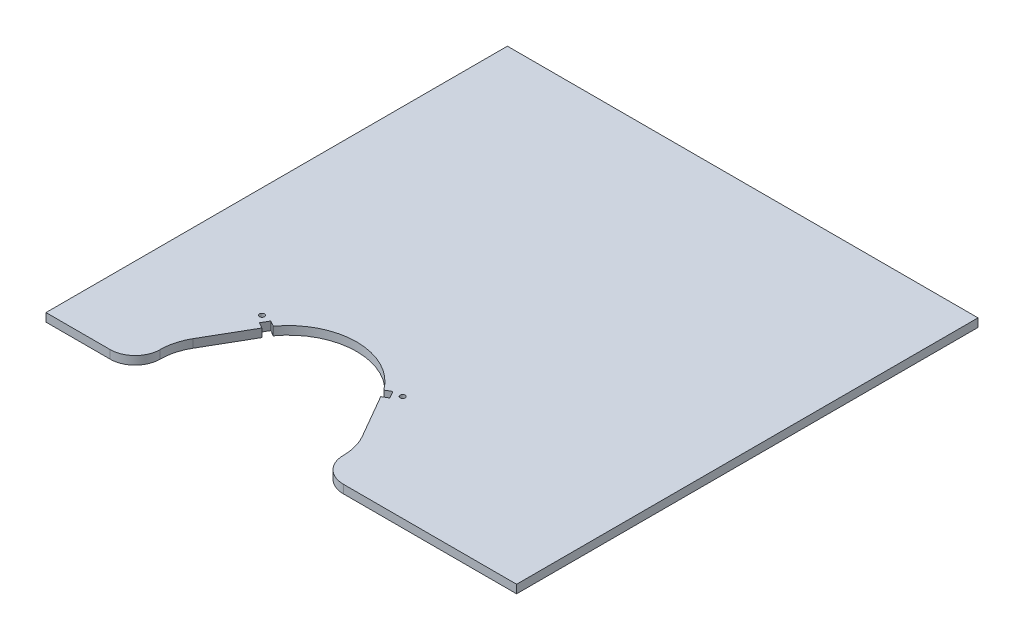
SolidWorks part; units mm, degrees
material "ABS PC"
ref_plane "Plan de face" through (0, 0, 0) normal (0, 0, 1) x (1, 0, 0)
ref_plane "Plan de dessus" through (0, 0, 0) normal (0, 1, 0) x (1, 0, 0)
ref_plane "Plan de droite" through (0, 0, 0) normal (1, 0, 0) x (0, 0, -1)
sketch "Esquisse1" plane through (0, 0, 0) normal (0, 1, 0) x (1, 0, 0)
  line L1 (-140.5, 31.9) -> (141.9979, 31.9)
  line L2 (-140.5, 31.9) -> (-140.5, -245.0829)
  line L3 (-140.5, -245.0829) -> (141.9979, -245.0829)
  line L4 (141.9979, 31.9) -> (141.9979, -245.0829)
  line L5 (38, -245.0829) -> (54.7016, -245.0829) construction
  line L6 (99.5, 31.9) -> (113.5, 31.9) construction
  arc A0 (-32, -23.5) -> (-95.029, -220.3153) centre (-32, -132) ccw construction
extrude "Boss.-Extru.1" add sketch "Esquisse1" along normal blind 5
sketch "Esquisse2" plane through (0, 0, 0) normal (0, 1, 0) x (1, 0, 0)
  line L3 (-65.1815, -184) -> (-68.6457, -182)
  line L4 (-68.6457, -182) -> (-71.1457, -186.3301)
  line L5 (-71.1457, -186.3301) -> (-67.6815, -188.3301)
  line L7 (-32, -132) -> (-32, -245.0829) construction
  line L8 (-65.1815, -184) -> (-67.6815, -188.3301) construction
  line L9 (-62.6323, -132) -> (62.6323, -132) construction
  line L10 (-32, -62.6323) -> (-32, 62.6323) construction
  line L11 (-67.6815, -188.3301) -> (-82.8539, -214.6094)
  line L13 (-65.1815, -184) -> (-61.7174, -186) construction
  line L14 (-32, -168.5125) -> (-32, -231.5125) construction
  line L16 (140.1, -245.0829) -> (-140.1, -245.0829) construction
  line L17 (-140.5, -245.0829) -> (141.9979, -245.0829) construction
  line L18 (1.1815, -184) -> (-2.2826, -186) construction
  line L20 (1.1815, -184) -> (3.6815, -188.3301) construction
  line L21 (3.6815, -188.3301) -> (18.8539, -214.6094)
  line L22 (7.1457, -186.3301) -> (3.6815, -188.3301)
  line L23 (4.6457, -182) -> (7.1457, -186.3301)
  line L24 (1.1815, -184) -> (4.6457, -182)
  line L25 (-69.8957, -184.1651) -> (-74.2258, -181.6651) construction
  line L26 (-102, -245.0829) -> (38, -245.0829)
  arc A1 (1.1815, -184) -> (-65.1815, -184) centre (-32, -208.0829) ccw
  arc A2 (-102, -245.0829) -> (-87, -230.0829) centre (-102, -230.0829) ccw
  arc A3 (-102, -245.0829) -> (-93.2863, -217.8734) centre (-102, -230.0829) ccw construction
  arc A4 (-87, -230.0829) -> (-82.8539, -214.6094) centre (-56.0531, -230.0829) cw
  arc A5 (23, -230.0829) -> (18.8539, -214.6094) centre (-7.9469, -230.0829) ccw
  arc A6 (38, -245.0829) -> (23, -230.0829) centre (38, -230.0829) cw
  circle A8 centre (-74.2258, -181.6651) radius 1.5
  circle A10 centre (10.2258, -181.6651) radius 1.5
  dimension "D4" = 41
  dimension "D8" = 5
  dimension "D9" = 3
  dimension "D1" = 4
  dimension "D2" = 52
  dimension "D3" = 37
  dimension "D5" = 90
  dimension "D6" = 5
  dimension "D7" = 30
extrude "Enlèv. mat.-Extru.2" cut sketch "Esquisse2" along normal through all
sketch "Esquisse3" plane through (0, 5, 0) normal (0, 1, 0) x (1, 0, 0)
  line L0 (-43.6093, -121.8429) -> (-36.5805, -137.9388)
  spline S0 degree 3 poles (259.3192, -1110.1176) (-417.1862, 235.5219) (-98.629, -194.1466) (-41.7351, -156.0551) (-41.3695, -155.7814) (-40.3208, -154.9029) (-39.696, -154.2528) (-38.8689, -153.1819) (-38.612, -152.8087) (-38.1363, -152.0291) (-37.9205, -151.6275) (-37.3411, -150.4003) (-37.0434, -149.5472) (-36.7214, -148.2184) (-36.6357, -147.7701) (-36.5052, -146.8774) (-36.4599, -146.4309) (-36.4039, -145.5376) (-36.3931, -145.0908) (-36.398, -144.4204) (-36.4039, -144.1969) (-36.4131, -143.7499) (-36.4173, -143.5265) (-37.0702, -106.8101) (-30.0085, -70.385) (-1030.1845, -25.1048) knots -9.338808 -9.338808 -9.338808 -9.338808 0.0625 0.0625 0.125 0.125 0.25 0.25 0.3125 0.3125 0.375 0.375 0.5 0.5 0.5625 0.5625 0.625 0.625 0.6875 0.6875 0.71875 0.71875 0.75 0.75 5.8528 5.8528 5.8528 5.8528 only from (-43.2724, -157) to (-36.5805, -137.9388)
  spline S1 degree 3 poles (-43.2724, -157) (-42.8739, -156.7891) (-42.4866, -156.5582) (-41.7351, -156.0551) (-41.3695, -155.7814) (-40.3208, -154.9029) (-39.696, -154.2528) (-38.8689, -153.1819) (-38.612, -152.8087) (-38.1363, -152.0291) (-37.9205, -151.6275) (-37.3411, -150.4003) (-37.0434, -149.5472) (-36.7214, -148.2184) (-36.6357, -147.7701) (-36.5052, -146.8774) (-36.4599, -146.4309) (-36.4039, -145.5376) (-36.3931, -145.0908) (-36.398, -144.4204) (-36.4039, -144.1969) (-36.4131, -143.7499) (-36.4173, -143.5265) (-36.4531, -141.5151) (-36.4664, -139.7274) (-36.5805, -137.9388) knots 0 0 0 0 0.0625 0.0625 0.125 0.125 0.25 0.25 0.3125 0.3125 0.375 0.375 0.5 0.5 0.5625 0.5625 0.625 0.625 0.6875 0.6875 0.71875 0.71875 0.75 0.75 1 1 1 1
  spline S2 degree 3 poles (-807.3976, -768.0821) (-207.7729, -356.7555) (-8.3852, -175.0827) (-57.4082, -99.0169) (-148.0414, -109.2326) (443.6615, -997.8773) knots -29.638124 -29.638124 -29.638124 -29.638124 0.5 0.5 17.046376 17.046376 17.046376 17.046376 only from (-43.2724, -157) to (-41.788, -123.6579)
  spline S3 degree 3 poles (428.8763, 759.4954) (-1074.6496, -1054.7702) (825.3665, 795.7235) (-610.7654, -945.9757) knots -98.67185 -98.67185 -98.67185 -98.67185 56.526799 56.526799 56.526799 56.526799 only from (-43.6093, -121.8429) to (-41.788, -123.6579)
  spline S4 degree 3 poles (-592.9003, -957.4703) (-128.9476, -383.168) (4.8408, -155.2068) (-46.1416, -119.9262) (-46.8207, -119.511) (-48.213, -118.7599) (-48.9275, -118.4229) (-50.3918, -117.8234) (-51.1435, -117.5604) (-53.4408, -116.8882) (-54.9943, -116.6022) (-57.3558, -116.4039) (-58.1482, -116.3765) (-59.7437, -116.4015) (-60.5372, -116.4541) (-62.8905, -116.7272) (-64.4299, -117.0612) (-66.6924, -117.8031) (-67.441, -118.0917) (-68.8899, -118.7352) (-69.594, -119.0917) (-70.9637, -119.8707) (-71.629, -120.2935) (-72.5964, -120.9799) (-72.9139, -121.2173) (-73.538, -121.7106) (-73.8456, -121.9674) (-75.3374, -123.2854) (-76.3911, -124.4538) (-77.7735, -126.368) (-78.2014, -127.0328) (-78.9877, -128.4193) (-79.344, -129.1356) (-79.8177, -130.2329) (-79.9655, -130.6032) (-80.2453, -131.3508) (-80.3755, -131.7281) (-80.6512, -132.4785) (-80.7876, -132.854) (-80.9715, -133.4214) (-81.0296, -133.6112) (-81.1394, -133.9921) (-81.1903, -134.1834) (-81.2671, -134.571) (-81.2968, -134.7665) (-81.3503, -135.1588) (-81.3728, -135.3558) (-81.4279, -135.9494) (-81.451, -136.3479) (-81.4748, -137.1494) (-81.4747, -137.5539) (-81.4511, -138.358) (-81.4278, -138.7584) (-81.3236, -139.9543) (-81.2088, -140.7447) (-80.9695, -141.9203) (-80.8785, -142.3104) (-80.6736, -143.0873) (-80.5593, -143.4752) (-79.9356, -145.3864) (-79.272, -146.8333) (-78.2379, -148.5399) (-78.0207, -148.876) (-77.5652, -149.5378) (-77.3263, -149.8643) (-76.5864, -150.8159) (-76.0605, -151.4164) (-74.944, -152.5502) (-74.3536, -153.0838) (-73.4193, -153.8335) (-73.0997, -154.0749) (-72.4436, -154.5402) (-72.1066, -154.7641) (-11.8281, -192.2778) (199.3038, 107.0716) (520.6383, 651.7994) knots -2.36371 -2.36371 -2.36371 -2.36371 0.03125 0.03125 0.0625 0.0625 0.09375 0.09375 0.125 0.125 0.1875 0.1875 0.21875 0.21875 0.25 0.25 0.3125 0.3125 0.34375 0.34375 0.375 0.375 0.40625 0.40625 0.421875 0.421875 0.4375 0.4375 0.5 0.5 0.53125 0.53125 0.5625 0.5625 0.578125 0.578125 0.59375 0.59375 0.609375 0.609375 0.617187 0.617187 0.625 0.625 0.632812 0.632812 0.640625 0.640625 0.65625 0.65625 0.671875 0.671875 0.6875 0.6875 0.71875 0.71875 0.734375 0.734375 0.75 0.75 0.8125 0.8125 0.828125 0.828125 0.84375 0.84375 0.875 0.875 0.90625 0.90625 0.921875 0.921875 0.9375 0.9375 3.685484 3.685484 3.685484 3.685484 only from (-43.6093, -121.8429) to (-67.442, -157)
  spline S5 degree 3 poles (-290.9074, 811.8494) (-23.7595, -8.3246) (-10.5586, -148.5116) (-46.6193, -158.2511) (-47.123, -158.3592) (-48.1288, -158.5248) (-48.6334, -158.5826) (-50.1515, -158.6913) (-51.1697, -158.6772) (-52.7021, -158.5709) (-53.2119, -158.5215) (-54.2295, -158.4067) (-54.7378, -158.3451) (-55.7572, -158.2514) (-56.2683, -158.22) (-57.2926, -158.1841) (-57.8057, -158.1783) (-59.3452, -158.1657) (-60.3714, -158.1559) (-62.416, -158.0302) (-63.4345, -157.9162) (-64.9553, -157.6541) (-65.463, -157.5494) (-147.8031, -137.2176) (-27.4964, 379.8007) (-662.8731, -960.4052) knots -4.366066 -4.366066 -4.366066 -4.366066 0.125 0.125 0.1875 0.1875 0.25 0.25 0.375 0.375 0.4375 0.4375 0.5 0.5 0.5625 0.5625 0.625 0.625 0.75 0.75 0.875 0.875 0.9375 0.9375 11.160115 11.160115 11.160115 11.160115 only from (-43.2724, -157) to (-67.442, -157)
  spline S7 degree 3 poles (-43.2724, -157) (-44.1824, -157.4815) (-45.1345, -157.85) (-46.6193, -158.2511) (-47.123, -158.3592) (-48.1288, -158.5248) (-48.6334, -158.5826) (-50.1515, -158.6913) (-51.1697, -158.6772) (-52.7021, -158.5709) (-53.2119, -158.5215) (-54.2295, -158.4067) (-54.7378, -158.3451) (-55.7572, -158.2514) (-56.2683, -158.22) (-57.2926, -158.1841) (-57.8057, -158.1783) (-59.3452, -158.1657) (-60.3714, -158.1559) (-62.416, -158.0302) (-63.4345, -157.9162) (-64.9553, -157.6541) (-65.463, -157.5494) (-66.4638, -157.3023) (-66.9566, -157.1602) (-67.442, -157) knots 0 0 0 0 0.125 0.125 0.1875 0.1875 0.25 0.25 0.375 0.375 0.4375 0.4375 0.5 0.5 0.5625 0.5625 0.625 0.625 0.75 0.75 0.875 0.875 0.9375 0.9375 1 1 1 1
  spline S8 degree 3 poles (-43.6093, -121.8429) (-44.2029, -121.3224) (-44.8282, -120.8351) (-46.1416, -119.9262) (-46.8207, -119.511) (-48.213, -118.7599) (-48.9275, -118.4229) (-50.3918, -117.8234) (-51.1435, -117.5604) (-53.4408, -116.8882) (-54.9943, -116.6022) (-57.3558, -116.4039) (-58.1482, -116.3765) (-59.7437, -116.4015) (-60.5372, -116.4541) (-62.8905, -116.7272) (-64.4299, -117.0612) (-66.6924, -117.8031) (-67.441, -118.0917) (-68.8899, -118.7352) (-69.594, -119.0917) (-70.9637, -119.8707) (-71.629, -120.2935) (-72.5964, -120.9799) (-72.9139, -121.2173) (-73.538, -121.7106) (-73.8456, -121.9674) (-75.3374, -123.2854) (-76.3911, -124.4538) (-77.7735, -126.368) (-78.2014, -127.0328) (-78.9877, -128.4193) (-79.344, -129.1356) (-79.8177, -130.2329) (-79.9655, -130.6032) (-80.2453, -131.3508) (-80.3755, -131.7281) (-80.6512, -132.4785) (-80.7876, -132.854) (-80.9715, -133.4214) (-81.0296, -133.6112) (-81.1394, -133.9921) (-81.1903, -134.1834) (-81.2671, -134.571) (-81.2968, -134.7665) (-81.3503, -135.1588) (-81.3728, -135.3558) (-81.4279, -135.9494) (-81.451, -136.3479) (-81.4748, -137.1494) (-81.4747, -137.5539) (-81.4511, -138.358) (-81.4278, -138.7584) (-81.3236, -139.9543) (-81.2088, -140.7447) (-80.9695, -141.9203) (-80.8785, -142.3104) (-80.6736, -143.0873) (-80.5593, -143.4752) (-79.9356, -145.3864) (-79.272, -146.8333) (-78.2379, -148.5399) (-78.0207, -148.876) (-77.5652, -149.5378) (-77.3263, -149.8643) (-76.5864, -150.8159) (-76.0605, -151.4164) (-74.944, -152.5502) (-74.3536, -153.0838) (-73.4193, -153.8335) (-73.0997, -154.0749) (-72.4436, -154.5402) (-72.1066, -154.7641) (-70.4026, -155.8246) (-68.9612, -156.4988) (-67.442, -157) knots 0 0 0 0 0.03125 0.03125 0.0625 0.0625 0.09375 0.09375 0.125 0.125 0.1875 0.1875 0.21875 0.21875 0.25 0.25 0.3125 0.3125 0.34375 0.34375 0.375 0.375 0.40625 0.40625 0.421875 0.421875 0.4375 0.4375 0.5 0.5 0.53125 0.53125 0.5625 0.5625 0.578125 0.578125 0.59375 0.59375 0.609375 0.609375 0.617187 0.617187 0.625 0.625 0.632812 0.632812 0.640625 0.640625 0.65625 0.65625 0.671875 0.671875 0.6875 0.6875 0.71875 0.71875 0.734375 0.734375 0.75 0.75 0.8125 0.8125 0.828125 0.828125 0.84375 0.84375 0.875 0.875 0.90625 0.90625 0.921875 0.921875 0.9375 0.9375 1 1 1 1
  spline S9 degree 3 poles (-43.6093, -121.8429) (-42.965, -122.4079) (-42.3573, -123.0122) (-41.788, -123.6579) knots 0 0 0 0 1 1 1 1
  spline S10 degree 3 poles (-43.2724, -157) (-36.5667, -143.6885) (-35.7185, -133.4582) (-40.6323, -125.1822) (-41.1865, -124.3928) (-41.788, -123.6579) knots -4.04373 -4.04373 -4.04373 -4.04373 0.5 0.5 1 1 1 1
extrude "Enlèv. mat.-Extru.3" cut sketch "Esquisse3" against normal through all rebuild error yes
